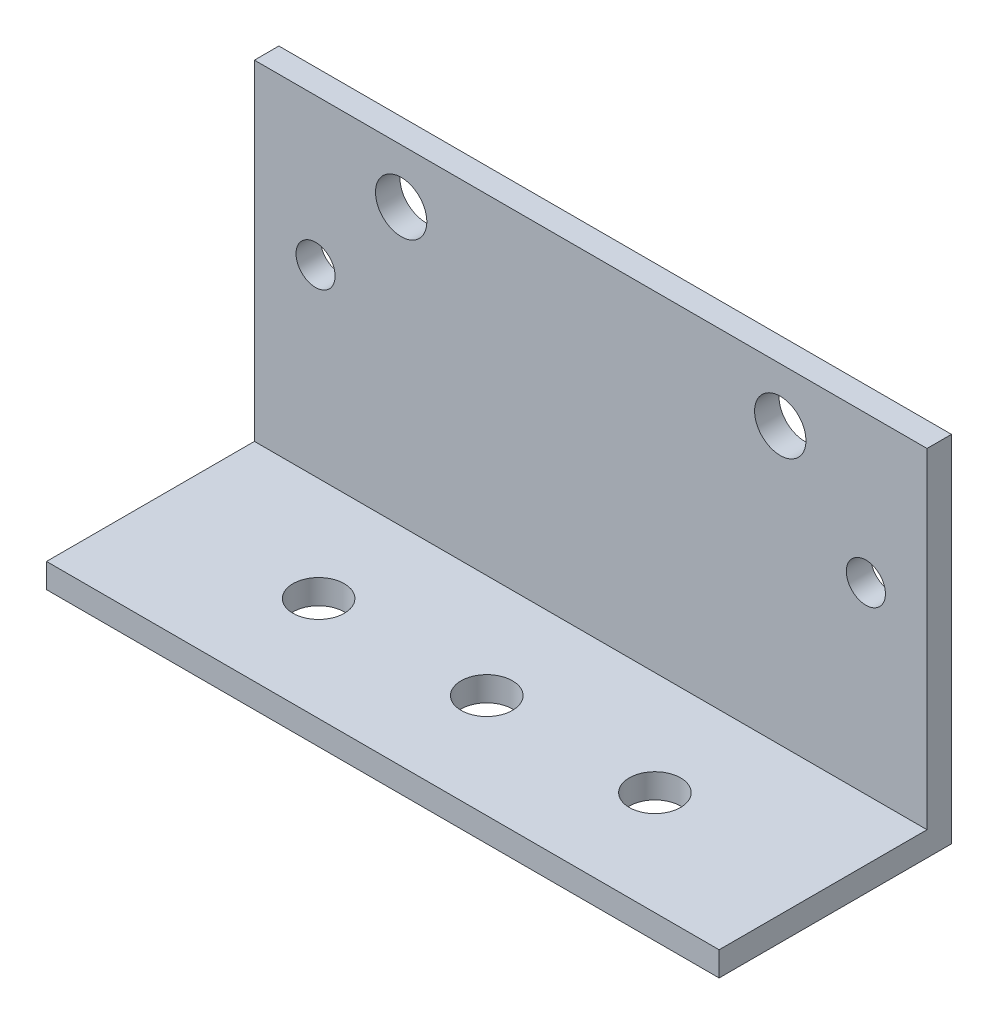
SolidWorks part; units mm, degrees
ref_plane "Front" through (0, 0, 0) normal (0, 0, 1) x (1, 0, 0)
ref_plane "Top" through (0, 0, 0) normal (0, 1, 0) x (1, 0, 0)
ref_plane "Right" through (0, 0, 0) normal (1, 0, 0) x (0, 0, -1)
sketch "Esquisse1" plane through (0, 0, 0) normal (0, 0, 1) x (1, 0, 0)
  line L0 (137.5, 145) -> (137.5, 0) construction
  line L1 (0, 0) -> (275, 0)
  line L2 (0, 0) -> (0, 145)
  line L3 (0, 145) -> (275, 145)
  line L4 (275, 0) -> (275, 145)
  circle A0 centre (60, 123) radius 10.5
  circle A1 centre (25, 85) radius 8
  circle A2 centre (250, 85) radius 8
  circle A3 centre (215, 123) radius 10.5
  dimension "D3" = 21
  dimension "D4" = 16
  dimension "D1" = 145
  dimension "D2" = 275
  dimension "D5" = 25
  dimension "D6" = 60
  dimension "D7" = 60
  dimension "D8" = 22
  dimension "D9" = 137.5
extrude "Boss.-Extru.1" add sketch "Esquisse1" along normal blind 10
sketch "Esquisse2" plane through (0, 0, 0) normal (0, 1, 0) x (1, 0, 0)
  line L1 (275, 0) -> (0, 0)
  line L2 (275, 0) -> (275, -95)
  line L3 (275, -95) -> (0, -95)
  line L4 (0, 0) -> (0, -95)
  dimension "D1" = 95
extrude "Boss.-Extru.2" add sketch "Esquisse2" along normal blind 10
ref_plane "Plan2" through (0, 10, 0) normal (0, 1, 0) x (1, 0, 0)
sketch "Esquisse4" plane through (0, 10, 0) normal (0, 1, 0) x (1, 0, 0)
  line L0 (275, -95) -> (275, -10) construction
  line L1 (0, -95) -> (275, -95) construction
  circle A0 centre (206.25, -52.5) radius 10.5
  circle A1 centre (137.5, -52.5) radius 10.5
  circle A2 centre (68.75, -52.5) radius 10.5
  point P5 (206.25, -47.2413)
  dimension "D1" = 21
  dimension "D2" = 68.75
  dimension "D4" = 42.5
  dimension "D3" = 3
extrude "Enlèv. mat.-Extru.1" cut sketch "Esquisse4" against normal through all
